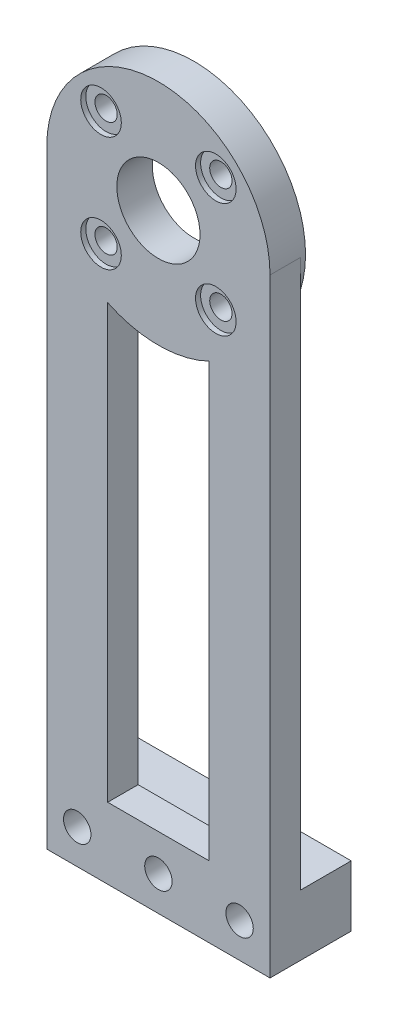
SolidWorks part; units mm, degrees
ref_plane "Front Plane" through (0, 0, 0) normal (0, 0, 1) x (1, 0, 0)
ref_plane "Top Plane" through (0, 0, 0) normal (0, 1, 0) x (1, 0, 0)
ref_plane "Right Plane" through (0, 0, 0) normal (1, 0, 0) x (0, 0, -1)
sketch "Sketch1" plane through (0, 0, 0) normal (0, 0, 1) x (1, 0, 0)
  line L0 (0, 30) -> (0, -30) construction
  line L2 (11, 30) -> (11, -30)
  line L4 (-11, 30) -> (-11, -30)
  line L5 (-11, -30) -> (11, -30)
  line L7 (11, -30) -> (-11, -30)
  line L8 (11, -30) -> (11, -24)
  line L9 (11, -24) -> (-11, -24)
  line L10 (-11, -30) -> (-11, -24)
  line L12 (-5, 19.6438) -> (-5, -23)
  line L13 (-5, -23) -> (5, -23)
  line L14 (5, 19.6438) -> (5, -23)
  circle A0 centre (0, 30) radius 11
  arc A1 (-5, 19.6438) -> (5, 19.6438) centre (0, 30) ccw
  point P0 (0, 0)
  point P2 (0, 0)
  point P8 (0, -30)
  point P18 (0, 0)
  dimension "D3" = 22
  dimension "D1" = 60
  dimension "D4" = 6
  dimension "D5" = 23
  dimension "D7" = 6
  dimension "D2" = 22
  dimension "D6" = 1
  dimension "D8" = 6
extrude "Boss-Extrude1" add sketch "Sketch1" along normal blind 3 contours L2 A0 L4 | A0 | A0 L0 L2 | L8 L7 L10 L9 region at (0, 30, 0) region at (10.4169, 3, 0)
extrude "Boss-Extrude2" add sketch "Sketch1<3>" against normal blind 0.5 contours A0 region at (0, 30, 0)
sketch "Sketch1<3>" plane through (0, 0, 0) normal (0, 0, 1) x (1, 0, 0) same geometry as "Sketch1"
sketch "Sketch2" plane through (0, 0, 3) normal (0, 0, 1) x (1, 0, 0)
  line L0 (0, 30) -> (5.6569, 35.6569) construction
  line L1 (11, 30) -> (11, -30) construction
  circle A0 centre (0, 30) radius 4.1
  circle A1 centre (5.6569, 35.6569) radius 1.1
  circle A2 centre (5.6569, 35.6569) radius 2
  dimension "D1" = 8.2
  dimension "D2" = 2.2
  dimension "D5" = 4
  dimension "D3" = 8
  dimension "D4" = 45
extrude "Cut-Extrude1" cut sketch "Sketch2" against normal up to surface (3.5 mm away) contours A0 | A1 region at (0, 30, 3) region at (5.6569, 35.6569, 3) up to face at (11, 30, -0.5)
extrude "Cut-Extrude2" cut sketch "Sketch2<3>" against normal offset from surface (0.5 mm away) 3 contours A2 A1 region at (3.7134, 35.6569, 3) up to face at (4.1, 30, -0.5)
sketch "Sketch2<3>" plane through (0, 0, 3) normal (0, 0, 1) x (1, 0, 0) same geometry as "Sketch2"
pattern_circular "CirPattern2" count 4 over 360 about axis through (0, 30, 3) along (0, 0, 1) of "Cut-Extrude2", "Cut-Extrude1"
extrude "Boss-Extrude3" add sketch "Sketch1<6>" against normal blind 5 contours L0 L9 L4 L5 | L9 L0 L7 L2 region at (-5.5, -27, 0) region at (5.5, -27, 0)
sketch "Sketch1<6>" plane through (0, 0, 0) normal (0, 0, 1) x (1, 0, 0) same geometry as "Sketch1"
sketch "Sketch4" plane through (0, 0, 3) normal (0, 0, 1) x (1, 0, 0)
  line L0 (-11, -30) -> (11, -30) construction
  circle A0 centre (0, -26.6) radius 1.35
  dimension "D2" = 2.7
  dimension "D1" = 3.4
extrude "Cut-Extrude4" cut sketch "Sketch4" against normal up to surface (8 mm away) up to face at (0, -27, -5)
pattern_linear "LPattern2" count 2 spacing 8 along (1, 0, 0) count 2 spacing 8 along (-1, 0, 0) of "Cut-Extrude4"
